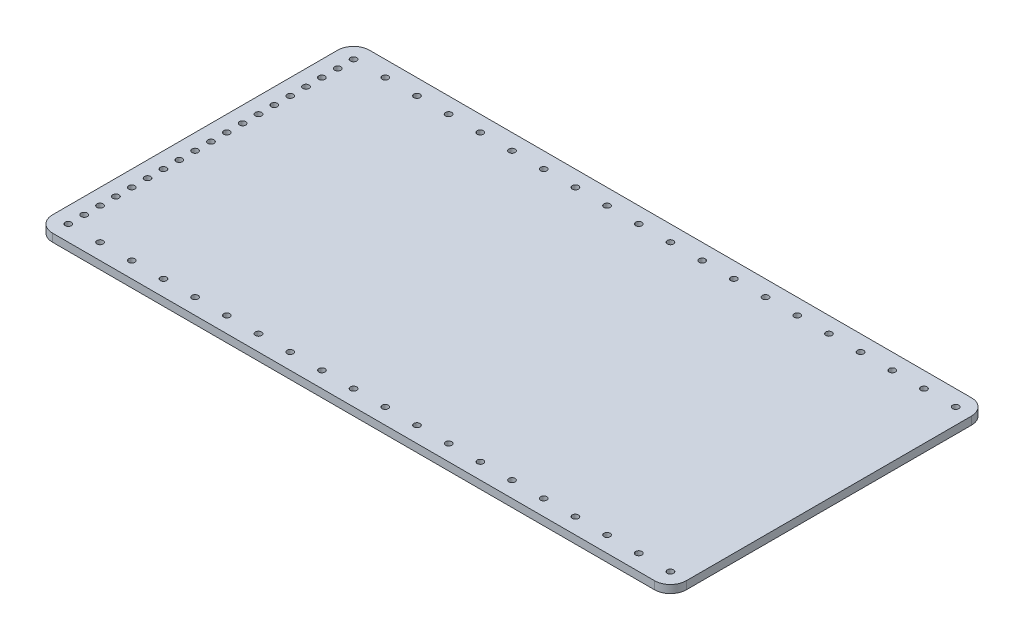
SolidWorks part; units mm, degrees
material "PC High Viscosity"
ref_plane "Front Plane" through (0, 0, 0) normal (0, 0, 1) x (1, 0, 0)
ref_plane "Top Plane" through (0, 0, 0) normal (0, 1, 0) x (1, 0, 0)
ref_plane "Right Plane" through (0, 0, 0) normal (1, 0, 0) x (0, 0, -1)
sketch "Sketch1" plane through (0, 0, 0) normal (0, 1, 0) x (1, 0, 0)
  line L1 (0, 0) -> (508, 0)
  line L2 (0, 0) -> (0, 254)
  line L3 (0, 254) -> (508, 254)
  line L4 (508, 0) -> (508, 254)
  dimension "D1" = 508
  dimension "D2" = 254
extrude "Boss-Extrude1" add sketch "Sketch1" along normal blind 6.35
sketch "Sketch3" plane through (0, 6.35, 0) normal (0, 1, 0) x (1, 0, 0)
  line L0 (508, 254) -> (0, 254) construction
  line L1 (0, 254) -> (0, 0) construction
  line L2 (12.7, 241.3) -> (38.1, 241.3) construction
  line L3 (12.7, 241.3) -> (12.7, 228.6) construction
  line L4 (12.7, 12.7) -> (38.1, 12.7) construction
  line L5 (12.7, 215.9) -> (12.7, 190.5) construction
  line L6 (495.3, 241.3) -> (495.3, 228.6) construction
  circle A0 centre (12.7, 241.3) radius 2.4892
  circle A1 centre (38.1, 241.3) radius 2.4892
  circle A2 centre (63.5, 241.3) radius 2.4892
  circle A3 centre (88.9, 241.3) radius 2.4892
  circle A4 centre (114.3, 241.3) radius 2.4892
  circle A5 centre (139.7, 241.3) radius 2.4892
  circle A6 centre (165.1, 241.3) radius 2.4892
  circle A7 centre (190.5, 241.3) radius 2.4892
  circle A8 centre (215.9, 241.3) radius 2.4892
  circle A9 centre (241.3, 241.3) radius 2.4892
  circle A10 centre (266.7, 241.3) radius 2.4892
  circle A11 centre (292.1, 241.3) radius 2.4892
  circle A12 centre (317.5, 241.3) radius 2.4892
  circle A13 centre (342.9, 241.3) radius 2.4892
  circle A14 centre (368.3, 241.3) radius 2.4892
  circle A15 centre (393.7, 241.3) radius 2.4892
  circle A16 centre (419.1, 241.3) radius 2.4892
  circle A17 centre (444.5, 241.3) radius 2.4892
  circle A18 centre (469.9, 241.3) radius 2.4892
  circle A19 centre (495.3, 241.3) radius 2.4892
  circle A23 centre (12.7, 228.6) radius 2.4892
  circle A24 centre (12.7, 215.9) radius 2.4892
  circle A25 centre (12.7, 203.2) radius 2.4892
  circle A26 centre (12.7, 190.5) radius 2.4892
  circle A27 centre (12.7, 177.8) radius 2.4892
  circle A28 centre (12.7, 165.1) radius 2.4892
  circle A29 centre (12.7, 152.4) radius 2.4892
  circle A30 centre (12.7, 139.7) radius 2.4892
  circle A31 centre (12.7, 127) radius 2.4892
  circle A32 centre (12.7, 114.3) radius 2.4892
  circle A33 centre (12.7, 101.6) radius 2.4892
  circle A56 centre (12.7, 215.9) radius 2.4892
  circle A57 centre (12.7, 190.5) radius 2.4892
  circle A58 centre (12.7, 165.1) radius 2.4892
  circle A59 centre (12.7, 139.7) radius 2.4892
  circle A60 centre (12.7, 114.3) radius 2.4892
  circle A61 centre (12.7, 88.9) radius 2.4892
  circle A62 centre (12.7, 63.5) radius 2.4892
  circle A63 centre (12.7, 38.1) radius 2.4892
  circle A64 centre (12.7, 12.7) radius 2.4892
  circle A65 centre (12.7, 88.9) radius 2.4892
  circle A66 centre (12.7, 76.2) radius 2.4892
  circle A67 centre (12.7, 63.5) radius 2.4892
  circle A68 centre (12.7, 50.8) radius 2.4892
  circle A69 centre (12.7, 38.1) radius 2.4892
  circle A70 centre (12.7, 25.4) radius 2.4892
  circle A71 centre (12.7, 12.7) radius 2.4892
  circle A72 centre (38.1, 12.7) radius 2.4892
  circle A73 centre (63.5, 12.7) radius 2.4892
  circle A74 centre (88.9, 12.7) radius 2.4892
  circle A75 centre (114.3, 12.7) radius 2.4892
  circle A76 centre (139.7, 12.7) radius 2.4892
  circle A77 centre (165.1, 12.7) radius 2.4892
  circle A78 centre (190.5, 12.7) radius 2.4892
  circle A79 centre (215.9, 12.7) radius 2.4892
  circle A80 centre (241.3, 12.7) radius 2.4892
  circle A81 centre (266.7, 12.7) radius 2.4892
  circle A82 centre (292.1, 12.7) radius 2.4892
  circle A83 centre (317.5, 12.7) radius 2.4892
  circle A84 centre (342.9, 12.7) radius 2.4892
  circle A85 centre (368.3, 12.7) radius 2.4892
  circle A86 centre (393.7, 12.7) radius 2.4892
  circle A87 centre (419.1, 12.7) radius 2.4892
  circle A88 centre (444.5, 12.7) radius 2.4892
  circle A89 centre (469.9, 12.7) radius 2.4892
  circle A90 centre (495.3, 12.7) radius 2.4892
  dimension "D1" = 12.7
  dimension "D2" = 4.9784
  dimension "D3" = 12.7
  dimension "D10" = 12.7
  dimension "D5" = 25.4
  dimension "D7" = 12.7
  dimension "D9" = 25.4
  dimension "D12" = 25.4
  dimension "D14" = 12.7
  dimension "D4" = 20
  dimension "D6" = 19
  dimension "D11" = 9
  dimension "D8" = 20
fillet "Fillet1" radius 12.7 4 edges at (508, 3.175, -254) (508, 3.175, 0) (0, 3.175, 0) (0, 3.175, -254)
extrude "Cut-Extrude2" cut sketch "Sketch3" against normal through all contours A25 | A24 | A23 | A0 | A1 | A2 | A3 | A4 | A64 | A70 | A63 | A68 | A62 | A72 | A73 | A74 | A33 | A32 | A31 | A30 | A28 | A29 | A27 | A26 | A61 | A66 | A90 | A89 | A88 | A87 | A86 | A85 | A84 | A83 | A82 | A81 | A80 | A79 | A75 | A76 | A77 | A78 | A5 | A6 | A7 | A8 | A9 | A10 | A11 | A12 | A13 | A14 | A15 | A16 | A17 | A18 | A19
